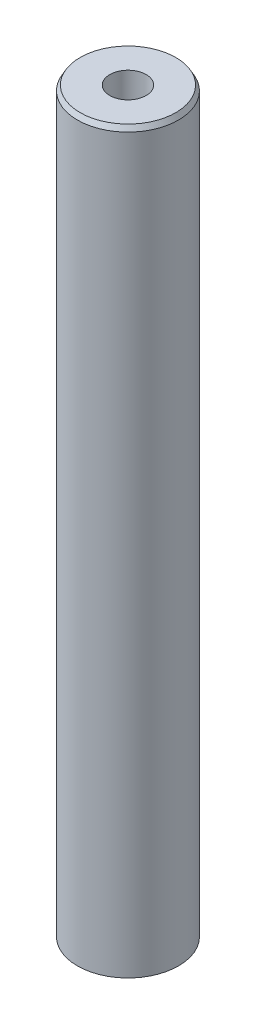
SolidWorks part; units mm, degrees
ref_plane "Front Plane" through (0, 0, 0) normal (0, 0, 1) x (1, 0, 0)
ref_plane "Top Plane" through (0, 0, 0) normal (0, 1, 0) x (1, 0, 0)
ref_plane "Right Plane" through (0, 0, 0) normal (1, 0, 0) x (0, 0, -1)
sketch "Sketch1" plane through (0, 0, 0) normal (0, 1, 0) x (1, 0, 0)
  circle A0 centre (0, 0) radius 15
  dimension "SHAFT_OD" = 30
extrude "Boss-Extrude1" add sketch "Sketch1" along normal blind 219.5831
sketch "Sketch2" plane through (0, 0, 0) normal (0, 1, 0) x (1, 0, 0)
  circle A0 centre (0, 0) radius 5.3964
  dimension "BORE_D" = 10.7927
extrude "Cut-Extrude1" cut sketch "Sketch2" along normal through all
chamfer "Chamfer1" distance 1.4891 angle 28.701 2 edges at (0, 219.5831, 15) (0, 0, 15) first distance on face at (0, 219.5831, 15) first distance on face at (0, 0, 5.3964)
